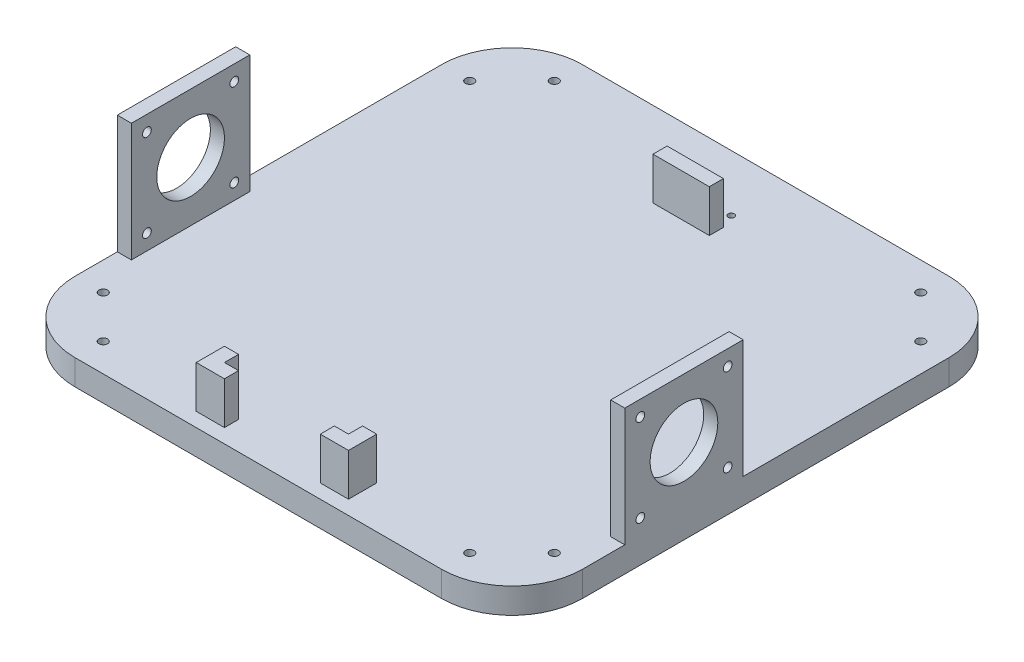
SolidWorks part; units mm, degrees
ref_plane "Front Plane" through (0, 0, 0) normal (0, 0, 1) x (1, 0, 0)
ref_plane "Top Plane" through (0, 0, 0) normal (0, 1, 0) x (1, 0, 0)
ref_plane "Right Plane" through (0, 0, 0) normal (1, 0, 0) x (0, 0, -1)
sketch "Sketch1" plane through (0, 0, 0) normal (0, 1, 0) x (1, 0, 0)
  line L1 (-65, -90) -> (65, -90)
  line L2 (-90, -65) -> (-90, 65)
  line L3 (-65, 90) -> (65, 90)
  line L4 (90, -65) -> (90, 65)
  arc A0 (-90, 65) -> (-65, 90) centre (-65, 65) cw
  arc A1 (65, 90) -> (90, 65) centre (65, 65) cw
  arc A2 (90, -65) -> (65, -90) centre (65, -65) cw
  arc A3 (-65, -90) -> (-90, -65) centre (-65, -65) cw
  point P4 (-90, 0)
  point P6 (0, 90)
  dimension "D3" = 25
  dimension "D1" = 180
  dimension "D2" = 180
extrude "Plate" add sketch "Sketch1" along normal blind 9
sketch "Sketch2" plane through (0, 9, 0) normal (0, 1, 0) x (1, 0, 0)
  line L0 (-7.747, 70) -> (7.747, 70) construction
  line L1 (0, 90) -> (0, 70) construction
  line L2 (-65, 90) -> (65, 90) construction
  circle A1 centre (-7.747, 70) radius 1.09
  circle A2 centre (7.747, 70) radius 1.09
  dimension "D3" = 2.18
  dimension "D1" = 15.494
  dimension "D2" = 20
extrude "Caster Holes" cut sketch "Sketch2" against normal through all
sketch "Sketch3" plane through (0, 9, 0) normal (0, 1, 0) x (1, 0, 0)
  line L0 (-65, 90) -> (-65, -90) construction
  line L1 (65, 90) -> (65, -90) construction
  line L2 (-90, 65) -> (90, 65) construction
  line L3 (-90, -65) -> (90, -65) construction
  circle A0 centre (-65, 80) radius 1.525
  circle A1 centre (-80, 65) radius 1.525
  circle A2 centre (80, 65) radius 1.525
  circle A3 centre (80, -65) radius 1.525
  circle A4 centre (65, 80) radius 1.525
  circle A5 centre (65, -80) radius 1.525
  circle A6 centre (-65, -80) radius 1.525
  circle A7 centre (-80, -65) radius 1.525
  dimension "D1" = 3.05
  dimension "D2" = 15
  dimension "D3" = 15
  dimension "D4" = 15
  dimension "D5" = 15
  dimension "D6" = 15
  dimension "D7" = 15
  dimension "D8" = 15
  dimension "D9" = 15
extrude "Hex Holes" cut sketch "Sketch3" against normal through all
sketch "Sketch4" plane through (0, 9, 0) normal (0, 1, 0) x (1, 0, 0)
  line L0 (-22, -80) -> (-17, -80)
  line L1 (-17, -80) -> (-17, -85)
  line L2 (-17, -85) -> (-27, -85)
  line L3 (-27, -85) -> (-27, -75)
  line L4 (-27, -75) -> (-22, -75)
  line L5 (-22, -75) -> (-22, -80)
  line L6 (17, -80) -> (22, -80)
  line L7 (22, -80) -> (22, -75)
  line L8 (22, -75) -> (27, -75)
  line L9 (27, -75) -> (27, -85)
  line L10 (27, -85) -> (17, -85)
  line L11 (17, -85) -> (17, -80)
  line L12 (-90, -65) -> (-90, 65) construction
  line L13 (-65, -90) -> (65, -90) construction
  line L14 (-65, 90) -> (65, 90) construction
  line L15 (-10, 60) -> (10, 60)
  line L16 (-10, 60) -> (-10, 65)
  line L17 (-10, 65) -> (10, 65)
  line L18 (10, 60) -> (10, 65)
  point P20 (0, 65)
  point P23 (0, 90)
  dimension "D1" = 44
  dimension "D2" = 5
  dimension "D3" = 63
  dimension "D4" = 5
  dimension "D5" = 140
  dimension "D6" = 5
  dimension "D7" = 20
extrude "Battery Holder" add sketch "Sketch4" along normal blind 15
sketch "Sketch5" plane through (-90, 0, 0) normal (-1, 0, 0) x (0, 0, 1)
  line L0 (-65, 9) -> (65, 9) construction
  line L1 (50, 9) -> (8, 9)
  line L2 (50, 9) -> (50, 51)
  line L3 (50, 51) -> (8, 51)
  line L4 (8, 9) -> (8, 51)
  line L5 (65, 9) -> (65, 0) construction
  circle A0 centre (29, 30) radius 12
  circle A1 centre (13.5, 45.5) radius 1.55
  circle A2 centre (44.5, 45.5) radius 1.55
  circle A3 centre (44.5, 14.5) radius 1.55
  circle A4 centre (13.5, 14.5) radius 1.55
  point P11 (29, 51)
  point P19 (0, 0)
  point P20 (8, 30)
  point P21 (0, 0)
  dimension "D4" = 24
  dimension "D5" = 3.1
  dimension "D1" = 42
  dimension "D2" = 42
  dimension "D3" = 15
  dimension "D6" = 5.5
  dimension "D7" = 5.5
  dimension "D8" = 5.5
  dimension "D9" = 5.5
extrude "Boss-Extrude2" add sketch "Sketch5" against normal blind 5
sketch "Sketch6" plane through (90, 0, 0) normal (1, 0, 0) x (0, 0, -1)
  line L0 (-8, 9) -> (-50, 9)
  line L1 (-8, 9) -> (-8, 51)
  line L2 (-8, 51) -> (-50, 51)
  line L3 (-50, 9) -> (-50, 51)
  line L4 (-65, 9) -> (-65, 0) construction
  line L5 (-65, 9) -> (65, 9) construction
  circle A0 centre (-29, 30) radius 12
  circle A1 centre (-44.5, 45.5) radius 1.55
  circle A2 centre (-13.5, 45.5) radius 1.55
  circle A3 centre (-13.5, 14.5) radius 1.55
  circle A4 centre (-44.5, 14.5) radius 1.55
  point P7 (-29, 51)
  point P15 (-50, 30)
  point P20 (0, 0)
  point P21 (0, 0)
  point P22 (-45.0588, 41.1873)
  point P23 (-40.7025, 47.9396)
  point P24 (0, 0)
  dimension "D6" = 3.1
  dimension "D7" = 24
  dimension "D1" = 15
  dimension "D2" = 42
  dimension "D3" = 42
  dimension "D4" = 5.5
  dimension "D5" = 5.5
  dimension "D8" = 5.5
  dimension "D9" = 5.5
extrude "Boss-Extrude3" add sketch "Sketch6" against normal blind 5
sketch "Sketch7" plane through (0, 0, 0) normal (0, -1, 0) x (1, 0, 0)
  line L0 (-65, -90) -> (65, -90) construction
  line L1 (0, 90) -> (0, -90) construction
  line L2 (-65, 90) -> (65, 90) construction
  circle A0 centre (0, -70) radius 11.6
  point P4 (0, 0)
  dimension "D2" = 23.2
  dimension "D1" = 20
extrude "Cut-Extrude1" cut sketch "Sketch7" against normal blind 2
